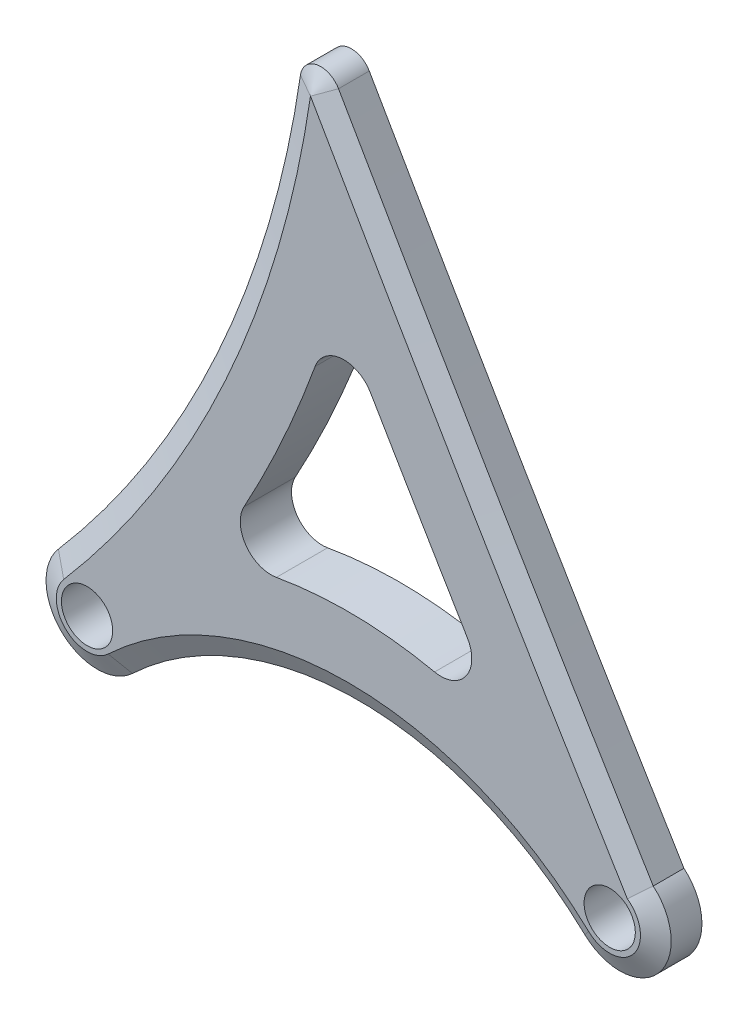
SolidWorks part; units mm, degrees
ref_plane "前基準面" through (0, 0, 0) normal (0, 0, 1) x (1, 0, 0)
ref_plane "上基準面" through (0, 0, 0) normal (0, 1, 0) x (1, 0, 0)
ref_plane "右基準面" through (0, 0, 0) normal (1, 0, 0) x (0, 0, -1)
sketch "草圖1" plane through (0, 0, 0) normal (0, 0, 1) x (1, 0, 0)
  line L0 (0, 0) -> (4.9118, 99.8793) construction
  line L1 (4.9118, 99.8793) -> (51, 0) construction
  line L2 (51, 0) -> (0, 0) construction
  line L3 (-3.3384, 27.9301) -> (-4.9911, 0.2985)
  line L4 (43.6186, 27.9301) -> (55.54, 2.0949)
  line L5 (0, -5) -> (51, -5)
  line L6 (43.6186, 27.9301) -> (62.2836, 27.9301)
  line L7 (-32.8905, 134.0085) -> (62.2836, 134.0085)
  line L8 (-32.8905, 134.0085) -> (-32.8905, 27.9301)
  line L9 (-32.8905, 27.9301) -> (-3.3384, 27.9301)
  line L10 (62.2836, 134.0085) -> (62.2836, 27.9301)
  circle A0 centre (51, 0) radius 2.5
  circle A1 centre (0, 0) radius 2.5
  arc A3 (51, -5) -> (55.54, 2.0949) centre (51, 0) ccw
  arc A4 (-4.9911, 0.2985) -> (0, -5) centre (0, 0) ccw
  circle A6 centre (0, 0) radius 5 construction
  circle A7 centre (51, 0) radius 5 construction
  point P8 (-3.3384, 27.9301)
  dimension "D4" = 5
  dimension "D1" = 51
  dimension "D2" = 100
  dimension "D3" = 110
  dimension "D5" = 2.5
extrude "填料-伸長1" add sketch "草圖1" along normal mid plane 5
sketch "草圖2" plane through (0, 0, 2.5) normal (0, 0, 1) x (1, 0, 0)
  arc A1 (51, -5) -> (55.54, 2.0949) centre (51, 0) ccw construction
  arc A2 (-4.9911, 0.2985) -> (0, -5) centre (0, 0) ccw construction
  arc A3 (47.5713, -3.6392) -> (54.2457, 3.8033) centre (51, 0) ccw
  arc A4 (-3.7942, 3.2564) -> (3.4287, -3.6392) centre (0, 0) ccw
  arc A5 (20.5222, 61.1313) -> (54.2457, 3.8033) centre (1817.85, 1079.836) ccw
  arc A6 (-3.7942, 3.2564) -> (20.5222, 61.1313) centre (-81.5058, 69.9531) ccw
  arc A8 (3.4287, -3.6392) -> (47.5713, -3.6392) centre (25.5, -27.0656) cw
  point P1 (29.5101, 58.0049)
  point P2 (20.5222, 61.1313)
extrude "除料-伸長1" cut sketch "草圖2" against normal blind 5 flip side to cut
sketch "草圖4" plane through (0, 0, 2.5) normal (0, 0, 1) x (1, 0, 0)
  arc A0 (47.5713, -3.6392) -> (3.4287, -3.6392) centre (25.5, -27.0656) ccw construction
  arc A1 (-3.7942, 3.2564) -> (20.5222, 61.1313) centre (-81.5058, 69.9531) ccw construction
  arc A3 (47.5713, -3.6392) -> (3.4287, -3.6392) centre (25.5, -27.0656) ccw construction
  arc A4 (-3.7942, 3.2564) -> (20.5222, 61.1313) centre (-81.5058, 69.9531) ccw construction
  arc A6 (33.9131, 12.2298) -> (18.4748, 12.5015) centre (25.5, -27.0656) ccw
  arc A7 (15.3195, 16.897) -> (22.2523, 32.2128) centre (-81.5058, 69.9531) ccw
  arc A9 (27.6612, 32.7021) -> (37.117, 16.7012) centre (1817.85, 1079.836) ccw
  arc A10 (53.0572, 2.1835) -> (-2.0572, 2.1835) centre (25.5, -27.0656) ccw construction
  arc A11 (37.117, 16.7012) -> (33.9131, 12.2298) centre (34.5412, 15.1634) cw
  arc A12 (2.2765, -1.9538) -> (28.4925, 60.4422) centre (-81.5058, 69.9531) ccw construction
  arc A13 (18.4748, 12.5015) -> (15.3195, 16.897) centre (17.9504, 15.4553) cw
  arc A14 (27.6612, 32.7021) -> (22.2523, 32.2128) centre (25.0716, 31.1874) ccw
  point P27 (16.9498, 74.5473)
  point P29 (49.3788, 7.9698)
  point P32 (0, 0)
  point P33 (8.8728, 59.9292)
  point P34 (0, 0)
  point P35 (2.246, 53.2764)
  point P36 (30.9277, 39.7976)
  point P38 (0, 0)
  point P39 (21.9666, 31.4287)
  dimension "D2" = 3
  dimension "D1" = 8
extrude "除料-伸長2" cut sketch "草圖4" against normal blind 5
fillet "圓角1" radius 2 1 edges at (20.5222, 61.1313, 0)
chamfer "導角1" distance 1 distance2 2 6 edges at (38.7025, 29.7024, 2.5) (11.6955, 27.5143, 2.5) (-3.4526, -3.6165, 2.5) (25.5, 5.1204, 2.5) (54.7224, -3.3382, 2.5) (21.4314, 56.8, 2.5)
chamfer "導角2" distance 2 distance2 1 6 edges at (11.6955, 27.5143, -2.5) (-3.4526, -3.6165, -2.5) (25.5, 5.1204, -2.5) (54.7224, -3.3382, -2.5) (38.7025, 29.7024, -2.5) (21.4314, 56.8, -2.5)
